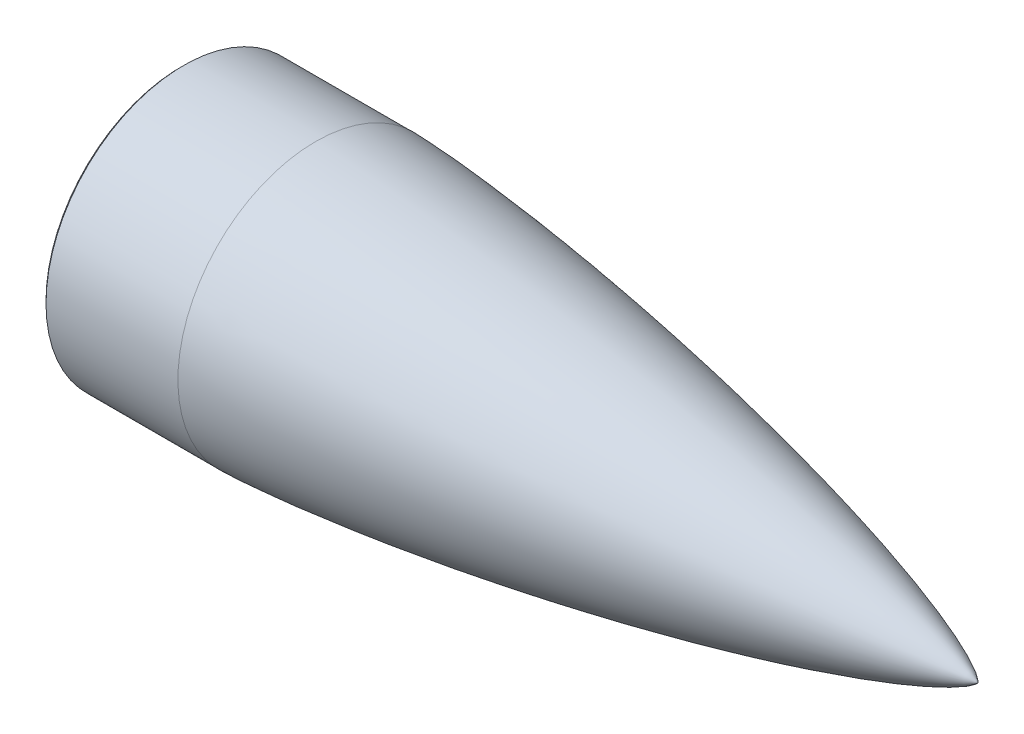
SolidWorks part; units mm, degrees
material "ABS"
ref_plane "Front Plane" through (0, 0, 0) normal (0, 0, 1) x (1, 0, 0)
ref_plane "Top Plane" through (0, 0, 0) normal (0, 1, 0) x (1, 0, 0)
ref_plane "Right Plane" through (0, 0, 0) normal (1, 0, 0) x (0, 0, -1)
ref_axis "Axis1" through (433.6458, 0, 0) along (-1, 0, 0)
sketch "Sketch10" plane through (0, 0, 0) normal (0, 0, 1) x (1, 0, 0)
  line L1 (-0.6328, 0) -> (486.9547, 0) construction
  line L3 (11.5124, 81.9998) -> (-82.7046, 81.9998)
  line L4 (409.3672, 0) -> (369.3672, 0)
  line L5 (-82.7046, 81.9998) -> (-82.7046, 84.9998)
  line L6 (-82.7046, 84.9998) -> (0.3953, 84.9998)
  line L7 (0.3953, 84.9998) -> (0.3953, 85.0999)
  spline S0 degree 4 poles (409.3672, 0) (409.3648, 0.0135) (409.3578, 0.0399) (409.336, 0.0903) (409.2914, 0.1737) (409.225, 0.2749) (409.1197, 0.4147) (408.9582, 0.6032) (408.7015, 0.8693) (408.2637, 1.2702) (407.5122, 1.8765) (406.1906, 2.8112) (403.8425, 4.2615) (399.695, 6.4869) (392.8359, 9.6822) (380.9943, 14.4963) (363.9414, 20.5008) (342.4882, 27.166) (317.6691, 34.0718) (292.0895, 40.5602) (266.3924, 46.565) (240.6012, 52.1496) (214.7301, 57.3514) (188.7894, 62.193) (166.0362, 66.123) (146.4971, 69.2728) (130.1914, 71.7482) (117.1331, 73.6367) (104.0615, 75.4303) (92.6123, 76.9131) (82.7905, 78.1186) (74.6001, 79.0771) (68.0446, 79.8153) (61.4857, 80.5233) (54.9234, 81.1999) (48.3578, 81.8429) (41.7888, 82.4502) (36.0379, 82.9479) (31.1064, 83.348) (26.9953, 83.6624) (23.7055, 83.9016) (20.0904, 84.1501) (16.7235, 84.365) (13.6048, 84.5484) (10.7347, 84.7027) (8.438, 84.8162) (6.1409, 84.9189) (4.1304, 84.9968) (2.4068, 85.054) (1.2574, 85.0831) (0.6827, 85.0963) (0.3953, 85.0999) knots 0 0 0 0 0 0.00013 0.00026 0.00052 0.0009 0.00128 0.001925 0.002882 0.004418 0.006927 0.011111 0.018279 0.030673 0.051704 0.083102 0.139909 0.202703 0.265496 0.32829 0.391083 0.453877 0.516671 0.579464 0.642258 0.673655 0.705051 0.736448 0.767845 0.799242 0.81494 0.830639 0.846337 0.862036 0.877734 0.893432 0.909131 0.924829 0.932678 0.940527 0.948377 0.956226 0.967169 0.972641 0.978113 0.983585 0.989056 0.994528 0.997264 1 1 1 1 1 construction
  spline S1 degree 4 poles (409.3672, 0) (409.3648, 0.0135) (409.3578, 0.0399) (409.336, 0.0903) (409.2914, 0.1737) (409.225, 0.2749) (409.1197, 0.4147) (408.9582, 0.6032) (408.7015, 0.8693) (408.2637, 1.2702) (407.5122, 1.8765) (406.1906, 2.8112) (403.8425, 4.2615) (399.695, 6.4869) (392.8359, 9.6822) (380.9943, 14.4963) (363.9414, 20.5008) (342.4882, 27.166) (317.6691, 34.0718) (292.0895, 40.5602) (266.3924, 46.565) (240.6012, 52.1496) (214.7301, 57.3514) (188.7894, 62.193) (166.0362, 66.123) (146.4971, 69.2728) (130.1914, 71.7482) (117.1331, 73.6367) (104.0615, 75.4303) (92.6123, 76.9131) (82.7905, 78.1186) (74.6001, 79.0771) (68.0446, 79.8153) (61.4857, 80.5233) (54.9234, 81.1999) (48.3578, 81.8429) (41.7888, 82.4502) (36.0379, 82.9479) (31.1064, 83.348) (26.9953, 83.6624) (23.7055, 83.9016) (20.0904, 84.1501) (16.7235, 84.365) (13.6048, 84.5484) (10.7347, 84.7027) (8.438, 84.8162) (6.1409, 84.9189) (4.1304, 84.9968) (2.4068, 85.054) (1.2574, 85.0831) (0.6827, 85.0963) (0.3953, 85.0999) knots 0 0 0 0 0 0.00013 0.00026 0.00052 0.0009 0.00128 0.001925 0.002882 0.004418 0.006927 0.011111 0.018279 0.030673 0.051704 0.083102 0.139909 0.202703 0.265496 0.32829 0.391083 0.453877 0.516671 0.579464 0.642258 0.673655 0.705051 0.736448 0.767845 0.799242 0.81494 0.830639 0.846337 0.862036 0.877734 0.893432 0.909131 0.924829 0.932678 0.940527 0.948377 0.956226 0.967169 0.972641 0.978113 0.983585 0.989056 0.994528 0.997264 1 1 1 1 1
  spline S2 degree 4 poles (369.3672, 0) (369.3652, 0.0123) (369.3594, 0.0365) (369.3406, 0.083) (369.3023, 0.1587) (369.2455, 0.2503) (369.1556, 0.3766) (369.0166, 0.5484) (368.7928, 0.7936) (368.4086, 1.1649) (367.7447, 1.7299) (366.576, 2.6016) (364.4928, 3.96) (360.8259, 6.0407) (354.8021, 9.0183) (344.4429, 13.5077) (329.552, 19.1285) (310.8251, 25.3986) (289.1412, 31.9337) (266.7785, 38.1061) (244.3013, 43.8469) (221.7319, 49.212) (199.0839, 54.2345) (176.3668, 58.9343) (156.4345, 62.7717) (139.3133, 65.8645) (125.0221, 68.3077) (113.5754, 70.1797) (102.115, 71.9664) (92.0753, 73.4517) (83.4614, 74.6659) (76.2775, 75.6363) (70.5268, 76.3867) (64.7727, 77.1101) (59.0151, 77.8049) (53.2539, 78.4695) (47.4891, 79.1019) (42.4416, 79.6247) (38.1129, 80.0488) (34.5039, 80.385) (31.6157, 80.6428) (28.4647, 80.911) (25.0506, 81.1843) (21.8654, 81.4195) (18.9092, 81.6177) (16.4448, 81.767) (14.7191, 81.8612) (13.2394, 81.9336) (12.2527, 81.9739) (11.7592, 81.993) (11.5124, 81.9998) knots 0 0 0 0 0 0.000135 0.00027 0.00054 0.00092 0.001299 0.001947 0.002931 0.004512 0.007081 0.01138 0.018708 0.031424 0.052705 0.084103 0.14091 0.203703 0.266497 0.329291 0.392084 0.454878 0.517672 0.580465 0.643259 0.674656 0.706052 0.737449 0.768846 0.800243 0.815941 0.831639 0.847338 0.863036 0.878735 0.894433 0.910132 0.92583 0.933679 0.941528 0.949378 0.957227 0.96792 0.978613 0.98396 0.989307 0.994653 0.997327 1 1 1 1 1 construction
  spline S3 degree 4 poles (369.3672, 0) (369.3652, 0.0123) (369.3594, 0.0365) (369.3406, 0.083) (369.3023, 0.1587) (369.2455, 0.2503) (369.1556, 0.3766) (369.0166, 0.5484) (368.7928, 0.7936) (368.4086, 1.1649) (367.7447, 1.7299) (366.576, 2.6016) (364.4928, 3.96) (360.8259, 6.0407) (354.8021, 9.0183) (344.4429, 13.5077) (329.552, 19.1285) (310.8251, 25.3986) (289.1412, 31.9337) (266.7785, 38.1061) (244.3013, 43.8469) (221.7319, 49.212) (199.0839, 54.2345) (176.3668, 58.9343) (156.4345, 62.7717) (139.3133, 65.8645) (125.0221, 68.3077) (113.5754, 70.1797) (102.115, 71.9664) (92.0753, 73.4517) (83.4614, 74.6659) (76.2775, 75.6363) (70.5268, 76.3867) (64.7727, 77.1101) (59.0151, 77.8049) (53.2539, 78.4695) (47.4891, 79.1019) (42.4416, 79.6247) (38.1129, 80.0488) (34.5039, 80.385) (31.6157, 80.6428) (28.4647, 80.911) (25.0506, 81.1843) (21.8654, 81.4195) (18.9092, 81.6177) (16.4448, 81.767) (14.7191, 81.8612) (13.2394, 81.9336) (12.2527, 81.9739) (11.7592, 81.993) (11.5124, 81.9998) knots 0 0 0 0 0 0.000135 0.00027 0.00054 0.00092 0.001299 0.001947 0.002931 0.004512 0.007081 0.01138 0.018708 0.031424 0.052705 0.084103 0.14091 0.203703 0.266497 0.329291 0.392084 0.454878 0.517672 0.580465 0.643259 0.674656 0.706052 0.737449 0.768846 0.800243 0.815941 0.831639 0.847338 0.863036 0.878735 0.894433 0.910132 0.92583 0.933679 0.941528 0.949378 0.957227 0.96792 0.978613 0.98396 0.989307 0.994653 0.997327 1 1 1 1 1
  dimension "D4" = 84.9998
  dimension "D1" = 85.0999
  dimension "D3" = 410
  dimension "D5" = 370
  dimension "D6" = 83.0999
  dimension "D2" = 3
revolve "Revolve1" add sketch "Sketch10" angle 360 about axis through (433.6458, 0, 0) along (-1, 0, 0)
chamfer "Chamfer1" distance 1.5 angle 45 1 edges at (-82.7046, 0, -84.9998)
equation "\"TubeDiameter\" = 6.5433in"
equation "\"D1@Sketch10\"=(\"TubeDiameter\"/2)+2mm"
equation "\"D6@Sketch10\"=\"TubeDiameter\"/2"
